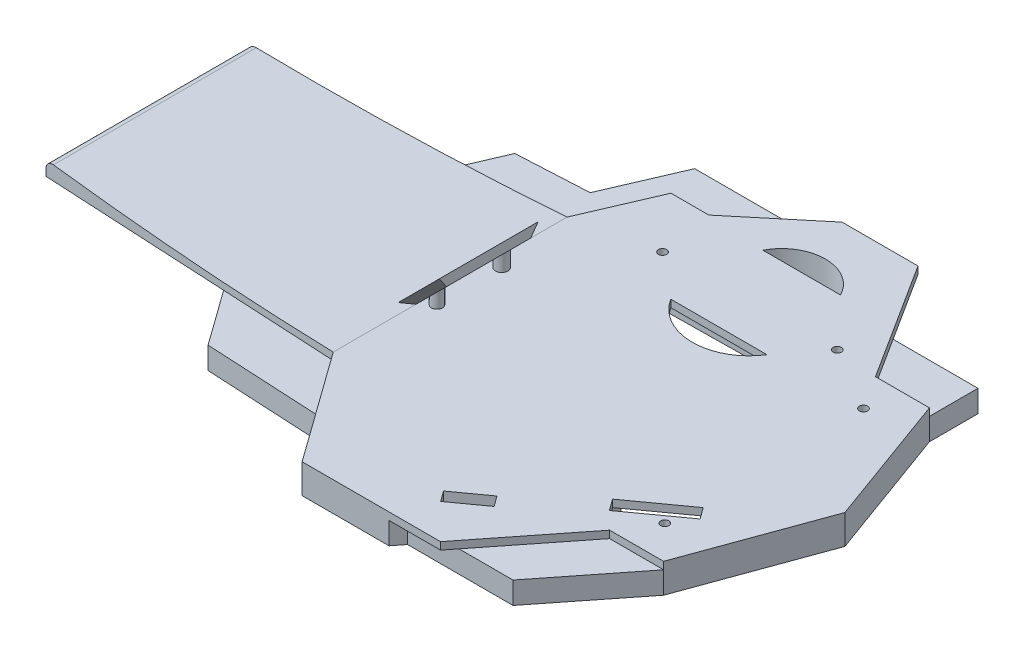
SolidWorks part; units mm, degrees
ref_plane "前视基准面" through (0, 0, 0) normal (0, 0, 1) x (1, 0, 0)
ref_plane "上视基准面" through (0, 0, 0) normal (0, 1, 0) x (1, 0, 0)
ref_plane "右视基准面" through (0, 0, 0) normal (1, 0, 0) x (0, 0, -1)
other "Configuration Table"
sketch "草图2" plane through (0, 0, 0) normal (0, 1, 0) x (1, 0, 0)
  line L0 (0, 0) -> (243.6421, 0) construction
  line L30 (176.8295, 36.1855) -> (82.5273, -31.8251) construction
  line L35 (141.8216, 68.0827) -> (121.1619, 68.0827)
  line L36 (176.8295, 36.1855) -> (190, 0)
  line L37 (104.1466, -61.9173) -> (82.5273, -31.8251)
  line L38 (82.5273, -31.8251) -> (0, -27.5)
  line L39 (0, -27.5) -> (0, 27.5)
  line L40 (0, 27.5) -> (82.5273, 31.8251)
  line L43 (190, 0) -> (176.8295, -36.1855)
  line L45 (82.5273, 31.8251) -> (91.0398, 51.6089)
  line L51 (104.1466, -61.9173) -> (190, 0) construction
  line L53 (141.8216, -61.9173) -> (104.1466, -61.9173)
  line L55 (82.5273, 31.8251) -> (342.4089, 31.8251) construction
  line L57 (176.8295, 36.1855) -> (176.8295, 0) construction
  line L58 (176.8295, 0) -> (176.8295, -36.1855) construction
  line L59 (82.5273, -31.8251) -> (342.4089, -31.8251) construction
  line L62 (91.0398, 51.6089) -> (101.351, 51.6089)
  line L63 (101.351, 51.6089) -> (121.1619, 68.0827)
  line L64 (141.8216, 68.0827) -> (162.1337, 36.1855)
  line L65 (162.1337, 36.1855) -> (176.8295, 36.1855)
  line L66 (176.8295, -36.1855) -> (162.1337, -36.1855)
  line L67 (162.1337, -36.1855) -> (141.8216, -61.9173)
  dimension "D1" = 190
  dimension "D2" = 130
  dimension "D4" = 55
  dimension "D6" = 93
  dimension "D7" = 93
  dimension "D8" = 140
extrude "凸台-拉伸1" add sketch "草图2" along normal blind 2
sketch "草图6" plane through (0, 2, 0) normal (0, 1, 0) x (1, 0, 0)
  line L0 (82.5273, 31.8251) -> (82.5273, -31.8251)
  line L1 (82.5273, -31.8251) -> (0, -27.5)
  line L2 (0, -27.5) -> (0, 27.5)
  line L3 (0, 27.5) -> (82.5273, 31.8251)
extrude "凸台-拉伸2" add sketch "草图6" along normal blind 2
sketch "草图7" plane through (0, 0, 0) normal (0, 0, 1) x (1, 0, 0)
  line L2 (82.5273, 2) -> (82.5273, 30.7408)
  line L3 (82.5273, 30.7408) -> (0, 4)
  spline S0 degree 2 poles (82.5273, 2) (41.2153, 1.0012) (0, 4) knots 0 0 0 1 1 1
extrude "切除-拉伸3" cut sketch "草图7" against normal through all both and the other way through all
fillet "圆角1" radius 2 1 edges at (0, 4, 0)
ref_plane "基准面3" through (0, -12, 0) normal (0, -1, 0) x (-1, 0, 0)
sketch "草图10" plane through (0, 0, 0) normal (0, -1, 0) x (1, 0, 0)
  line L0 (0, 27.5) -> (82.5273, 31.8251)
  line L1 (82.5273, 31.8251) -> (171.8529, 31.8251)
  line L2 (171.8529, 31.8251) -> (171.8529, -31.8251)
  line L3 (171.8529, -31.8251) -> (82.5273, -31.8251)
  line L4 (82.5273, -31.8251) -> (0, -27.5)
  line L5 (0, -27.5) -> (0, 27.5)
sketch "草图12" plane through (0, 2, 0) normal (0, 1, 0) x (1, 0, 0)
  line L0 (176.8295, 36.1855) -> (82.5273, -31.8251)
  line L1 (190, 0) -> (104.1466, -61.9173)
  line L2 (183.4148, 18.0928) -> (93.337, -46.8712) construction
  line L3 (190, 0) -> (176.8295, 36.1855) construction
  line L4 (82.5273, -31.8251) -> (104.1466, -61.9173) construction
sketch "草图13" plane through (0, 0, 0) normal (0, -1, 0) x (1, 0, 0)
  line L0 (53.5015, -30.3039) -> (58.4123, -41.717)
  line L1 (82.5273, -31.8251) -> (0, -27.5) construction
  line L2 (58.4123, -41.717) -> (77.9269, -42.7397)
  line L3 (77.9269, -42.7397) -> (86.4844, -62.6282)
  line L4 (86.4844, -62.6282) -> (136.1647, -62.6282)
  line L5 (176.8295, 36.1855) -> (190, 0)
  line L6 (190, 0) -> (176.8295, -36.1855)
  line L7 (136.1647, -62.6282) -> (144.5841, -49.4069)
  line L8 (144.5841, -49.4069) -> (176.8295, -49.4069)
  line L9 (176.8295, -49.4069) -> (176.8295, -36.1855)
  line L11 (176.8295, 36.1855) -> (158.7432, 59.0976)
  line L12 (158.7432, 59.0976) -> (130.0164, 59.0976)
  line L13 (130.0164, 59.0976) -> (127.7906, 61.9173)
  line L14 (104.1466, 61.9173) -> (141.8216, 61.9173) construction
  line L15 (127.7906, 61.9173) -> (104.1466, 61.9173)
  line L16 (104.1466, 61.9173) -> (93.337, 46.8712)
  line L17 (93.337, 46.8712) -> (61.8459, 45.2208)
  line L18 (61.8459, 45.2208) -> (51.0363, 30.1747)
  line L19 (0, 27.5) -> (82.5273, 31.8251) construction
  line L20 (51.0363, 30.1747) -> (171.8529, 31.8251)
  line L21 (171.8529, 31.8251) -> (171.8529, -31.8251)
  line L22 (171.8529, -31.8251) -> (53.5015, -30.3039)
extrude "凸台-拉伸4" add sketch "草图13" along normal blind 6 contours L18 L20 L21 L22 L0 L2 L3 L4 L7 L8 L9 L6 L5 L11 L12 L13 L15 L16 L17
sketch "草图17" plane through (0, 2, 0) normal (0, 1, 0) x (1, 0, 0)
  line L3 (116.0112, 26.5953) -> (142.1812, 26.5953)
  line L4 (138.1274, 50.6813) -> (116.9896, 50.6813)
  arc A1 (116.0112, 26.5953) -> (142.1812, 26.5953) centre (129.0962, 34.7996) ccw
  arc A2 (116.9896, 50.6813) -> (138.1274, 50.6813) centre (127.5585, 45.2443) cw
sketch "草图18" plane through (0, 2, 0) normal (0, 1, 0) x (1, 0, 0)
  line L4 (169.5639, -18.1259) -> (155.2183, -28.4719)
  line L5 (171.8094, -21.2395) -> (169.5639, -18.1259)
  line L6 (157.4639, -31.5855) -> (171.8094, -21.2395)
  line L7 (155.2183, -28.4719) -> (157.4639, -31.5855)
  line L8 (169.5639, -18.1259) -> (155.2183, -28.4719)
  line L9 (171.8094, -21.2395) -> (169.5639, -18.1259)
  line L10 (157.4639, -31.5855) -> (171.8094, -21.2395)
  line L11 (155.2183, -28.4719) -> (157.4639, -31.5855)
  line L12 (130.3021, -49.5646) -> (132.3616, -52.4203)
  line L13 (132.3616, -52.4203) -> (140.8147, -46.3239)
  line L14 (140.8147, -46.3239) -> (138.7552, -43.4683)
  line L15 (138.7552, -43.4683) -> (130.3021, -49.5646)
  line L16 (130.3021, -49.5646) -> (132.3616, -52.4203)
  line L17 (132.3616, -52.4203) -> (140.8147, -46.3239)
  line L18 (140.8147, -46.3239) -> (138.7552, -43.4683)
  line L19 (138.7552, -43.4683) -> (130.3021, -49.5646)
  dimension "D1" = 0
  dimension "D2" = 0
extrude "切除-拉伸7" cut sketch "草图18" against normal through all
sketch "草图19" plane through (0, 2, 0) normal (0, 1, 0) x (1, 0, 0)
  line L0 (82.5273, -31.8251) -> (176.8295, 36.1855)
  line L1 (176.8295, 36.1855) -> (190, 0)
  line L2 (190, 0) -> (104.1466, -61.9173)
  line L3 (104.1466, -61.9173) -> (82.5273, -31.8251)
ref_plane "基准面4" through (40.2637, -40.2637, 0) normal (-0.7071, 0.7071, 0) x (0, 0, -1)
sketch "草图23" plane through (40.2637, -40.2637, 0) normal (-0.7071, 0.7071, 0) x (0, 0, -1)
  line L0 (-9.292, -59.7699) -> (13.6381, -59.7699)
  line L1 (-31.8251, -59.7699) -> (31.8251, -59.7699) construction
  line L2 (13.6381, -59.7699) -> (13.6381, -71.5206)
  line L3 (13.6381, -71.5206) -> (-9.292, -71.5206)
  line L4 (-9.292, -71.5206) -> (-9.292, -60.8098)
  line L5 (-9.292, -60.8098) -> (-9.292, -59.7699)
  point P7 (0, 0)
extrude "凸台-拉伸5" add sketch "草图23" along normal blind 2 draft 45 separate body draft outward yes
sketch "草图24" plane through (0, 2, 0) normal (0, 1, 0) x (1, 0, 0)
  circle A0 centre (85.4903, 11.0478) radius 1.6973
  circle A1 centre (85.4903, -6.5413) radius 1.5
  point P4 (0, 0)
  point P5 (0, 0)
  point P6 (85.4903, 11.0478)
  point P7 (85.4903, -6.5413)
  point P8 (0, 0)
  point P9 (0, 0)
extrude "凸台-拉伸11" add sketch "草图24" along normal up to surface (2.9629 mm away) separate body contours A0 | A1 region at (85.4903, 2, -11.0478) region at (85.4903, 2, 6.5413) up to face at (86.6818, 6.1545, -2.173)
ref_plane "基准面6" through (0, 4, 0) normal (0, 1, 0) x (1, 0, 0)
sketch "草图25" plane through (0, 4, 0) normal (0, 1, 0) x (1, 0, 0)
  line L1 (67.0613, -53.2409) -> (67.0613, 49.4655) construction
  line L2 (-9.3986, 0) -> (224.1358, 0) construction
  circle A0 centre (67.0613, -25.5664) radius 3
  circle A1 centre (67.0613, 25.5664) radius 3
  circle A2 centre (168.0155, 27.0476) radius 1
  circle A3 centre (168.0155, -27.0476) radius 1
  circle A4 centre (150.7888, 25.9399) radius 3
  circle A5 centre (150.7888, -25.9399) radius 3
  point P11 (168.0155, 27.0476)
  point P14 (168.0155, -27.0476)
extrude "切除-拉伸8" cut sketch "草图17" against normal through all contours L4 A2 | L4 A2 | A1 L3 | A1 L3 region at (129.0962, 2, -23.6319) region at (127.5585, 2, -53.332)
hole_wizard "#4-40 螺纹孔3" positions "草图25" profile "草图26" tap size "#4-40" standard "ANSI Inch" end condition through all
sketch "草图26" plane through (168.0155, 4, 27.0476) normal (1, 0, 0) x (0, 0, 1)
  line L0 (0, 0) -> (0, 10)
  line L1 (0, 10) -> (1.1303, 10)
  line L2 (1.1303, 10) -> (1.1303, 0)
  line L5 (1.1303, 0) -> (0, 0)
  line L11 (0, -6.35) -> (0, 107.95) construction
  dimension "通孔螺纹孔钻头直径" = 2.2606
  dimension "通孔螺纹孔钻头深度" = 10
cosmetic thread "孔螺纹线4" parameters "D2"=2.8448
cosmetic thread "孔螺纹线5" parameters "D2"=2.8448
sketch "草图29" plane through (0, 0, 0) normal (0, -1, 0) x (1, 0, 0)
  circle A0 centre (67.0613, 25.5664) radius 3
  circle A1 centre (67.0613, -25.5664) radius 3
  circle A2 centre (150.7888, 25.9399) radius 3
  circle A3 centre (150.7888, -25.9399) radius 3
extrude "凸台-拉伸14" add sketch "草图29" along normal blind 5 contours A0 | A1 | A2 | A3 region at (67.0613, 0, 25.5664) region at (67.0613, 0, -25.5664) region at (150.7888, 0, 25.9399) region at (150.7888, 0, -25.9399)
sketch "草图33" plane through (0, 2, 0) normal (0, 1, 0) x (1, 0, 0)
  point P0 (150.5968, 37.3353)
  point P3 (103.7494, 36.6082)
hole_wizard "#4-40 螺纹孔4" positions "草图33" profile "草图32" tap size "#4-40" standard "ANSI Inch" end condition through all
sketch "草图32" plane through (150.5968, 2, -37.3353) normal (1, 0, 0) x (0, 0, 1)
  line L0 (0, 0) -> (0, 8)
  line L1 (0, 8) -> (1.1303, 8)
  line L2 (1.1303, 8) -> (1.1303, 0)
  line L5 (1.1303, 0) -> (0, 0)
  line L11 (0, -6.35) -> (0, 107.95) construction
  dimension "通孔螺纹孔钻头直径" = 2.2606
  dimension "通孔螺纹孔钻头深度" = 8
cosmetic thread "孔螺纹线8" parameters "D2"=2.8448
cosmetic thread "孔螺纹线9" parameters "D2"=2.8448
sketch "草图36" plane through (0, 0, 0) normal (0, 1, 0) x (1, 0, 0)
  point P0 (176.7356, -15.6397)
  point P3 (122.1817, -55.0926)
hole_wizard "#4-40 螺纹孔5" positions "草图36" profile "草图35" tap size "#4-40" standard "ANSI Inch" end condition through all
sketch "草图35" plane through (176.7356, 0, 15.6397) normal (1, 0, 0) x (0, 0, 1)
  line L0 (0, 0) -> (0, 6)
  line L1 (0, 6) -> (1.1303, 6)
  line L2 (1.1303, 6) -> (1.1303, 0)
  line L5 (1.1303, 0) -> (0, 0)
  line L11 (0, -6.35) -> (0, 107.95) construction
  dimension "通孔螺纹孔钻头直径" = 2.2606
  dimension "通孔螺纹孔钻头深度" = 6
cosmetic thread "孔螺纹线10" parameters "D2"=2.8448
cosmetic thread "孔螺纹线11" parameters "D2"=2.8448
